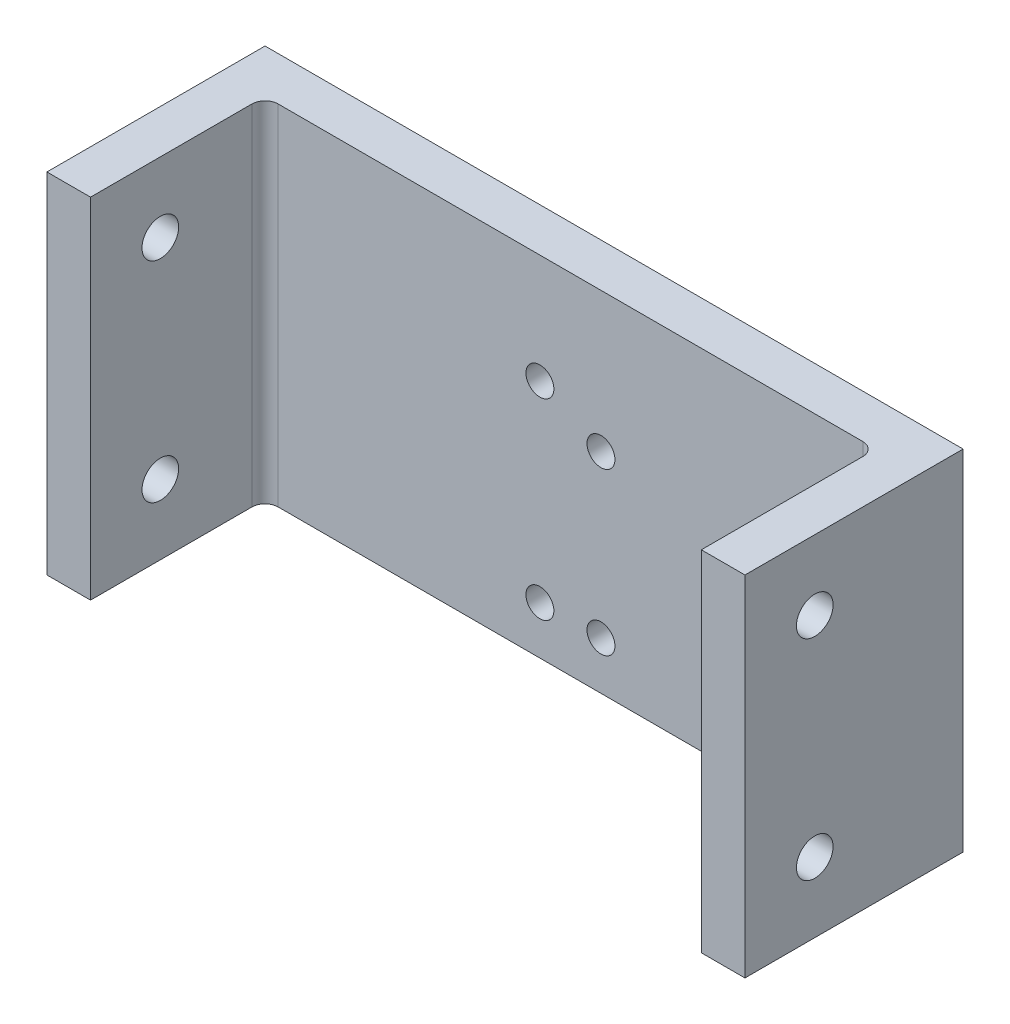
SolidWorks part; units mm, degrees
ref_plane "前视基准面" through (0, 0, 0) normal (0, 0, 1) x (1, 0, 0)
ref_plane "上视基准面" through (0, 0, 0) normal (0, 1, 0) x (1, 0, 0)
ref_plane "右视基准面" through (0, 0, 0) normal (1, 0, 0) x (0, 0, -1)
sketch "草图2" plane through (0, 37, 0) normal (0, 1, 0) x (1, 0, 0)
  line L0 (21, 0) -> (-59, 0)
  line L1 (-59, 161.75) -> (-59, -58.25) construction
  line L2 (-59, 0) -> (-59, -25)
  line L3 (-59, -25) -> (-54, -25)
  line L4 (21, -58.25) -> (21, -0.25) construction
  line L5 (21, -25) -> (21, 0)
  line L6 (-54, -25) -> (-54, -5)
  line L7 (-54, -5) -> (16, -5)
  line L8 (16, -5) -> (16, -25)
  line L9 (16, -25) -> (21, -25)
  dimension "D1" = 5
  dimension "D2" = 5
  dimension "D3" = 5
  dimension "D4" = 20
extrude "凸台-拉伸1" add sketch "草图2" against normal blind 40
fillet "圆角1" radius 1.5 2 edges at (16, 17, 5) (-54, 17, 5)
sketch "草图3" plane through (0, 0, 5) normal (0, 0, 1) x (1, 0, 0)
  circle A1 centre (-22.5, 2.5) radius 1.6
  circle A2 centre (-22.5, 24.5) radius 1.6
  dimension "D1" = 3.2
  dimension "D2" = 3.2
extrude "切除-拉伸1" cut sketch "草图3" against normal blind 40
sketch "草图4" plane through (-59, 0, 0) normal (-1, 0, 0) x (0, 0, 1)
  line L0 (0, 37) -> (25, 37) construction
  line L1 (0, -3) -> (25, -3) construction
  line L2 (25, -3) -> (25, 37) construction
  circle A0 centre (17, 29) radius 2.1
  circle A1 centre (17, 5) radius 2.1
  dimension "D1" = 8
  dimension "D2" = 4.2
  dimension "D3" = 4.2
  dimension "D4" = 8
  dimension "D5" = 8
  dimension "D6" = 8
extrude "切除-拉伸2" cut sketch "草图4" against normal blind 80
sketch "草图5" plane through (0, 0, 5) normal (0, 0, 1) x (1, 0, 0)
  circle A1 centre (-15.5, 2.5) radius 1.6
  circle A2 centre (-15.5, 21) radius 1.6
  dimension "D1" = 3.2
  dimension "D2" = 3.2
extrude "切除-拉伸3" cut sketch "草图5" against normal blind 80
